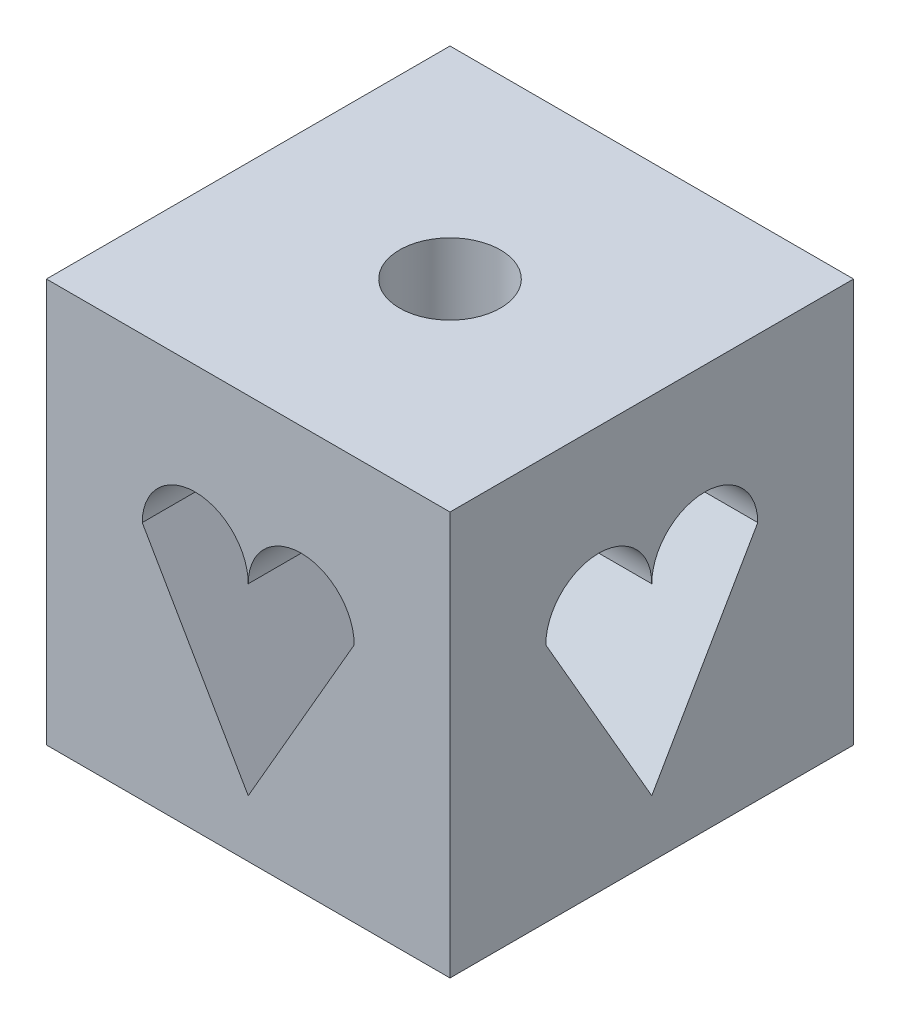
SolidWorks part; units mm, degrees
ref_plane "Front Plane" through (0, 0, 0) normal (0, 0, 1) x (1, 0, 0)
ref_plane "Top Plane" through (0, 0, 0) normal (0, 1, 0) x (1, 0, 0)
ref_plane "Right Plane" through (0, 0, 0) normal (1, 0, 0) x (0, 0, -1)
sketch "Sketch1" plane through (0, 0, 0) normal (0, 1, 0) x (1, 0, 0)
  line L1 (50, 50) -> (-50, 50)
  line L2 (50, 50) -> (50, -50)
  line L3 (50, -50) -> (-50, -50)
  line L4 (-50, 50) -> (-50, -50)
  line L5 (50, 50) -> (-50, -50) construction
  line L6 (50, -50) -> (-50, 50) construction
  point P0 (0, 0)
  dimension "D1" = 100
  dimension "D2" = 100
extrude "Boss-Extrude1" add sketch "Sketch1" along normal blind 100
sketch "Sketch2" plane through (0, 0, 50) normal (0, 0, 1) x (1, 0, 0)
  line L0 (0, 100) -> (0, 0) construction
  line L1 (-50, 100) -> (50, 100) construction
  line L2 (0, 14.1138) -> (-26.2601, 59.5976)
  line L4 (0, 14.1138) -> (26.2601, 59.5976)
  arc A0 (-26.2601, 59.5976) -> (0, 59.5976) centre (-13.13, 59.5976) cw
  arc A1 (26.2601, 59.5976) -> (0, 59.5976) centre (13.13, 59.5976) ccw
  dimension "D3" = 13.13
  dimension "D5" = 26.2601
  dimension "D1" = 30
  dimension "D2" = 45.4838
  dimension "D4" = 14.1138
ref_axis "Axis1" through (0, -5, 0) along (0, 1, 0)
extrude "Cut-Extrude1" cut sketch "Sketch2" against normal blind 50
pattern_circular "CirPattern1" count 4 over 360 about axis through (0, -5, 0) along (0, 1, 0) of "Cut-Extrude1"
sketch "Sketch3" plane through (0, 100, 0) normal (0, 1, 0) x (1, 0, 0)
  circle A0 centre (0, 0) radius 12.5
  dimension "D1" = 25
extrude "Cut-Extrude2" cut sketch "Sketch3" against normal blind 50
equation "\"D2@Sketch1\"=\"D1@Sketch1\""
equation "\"D1@Boss-Extrude1\"=\"D1@Sketch1\""
